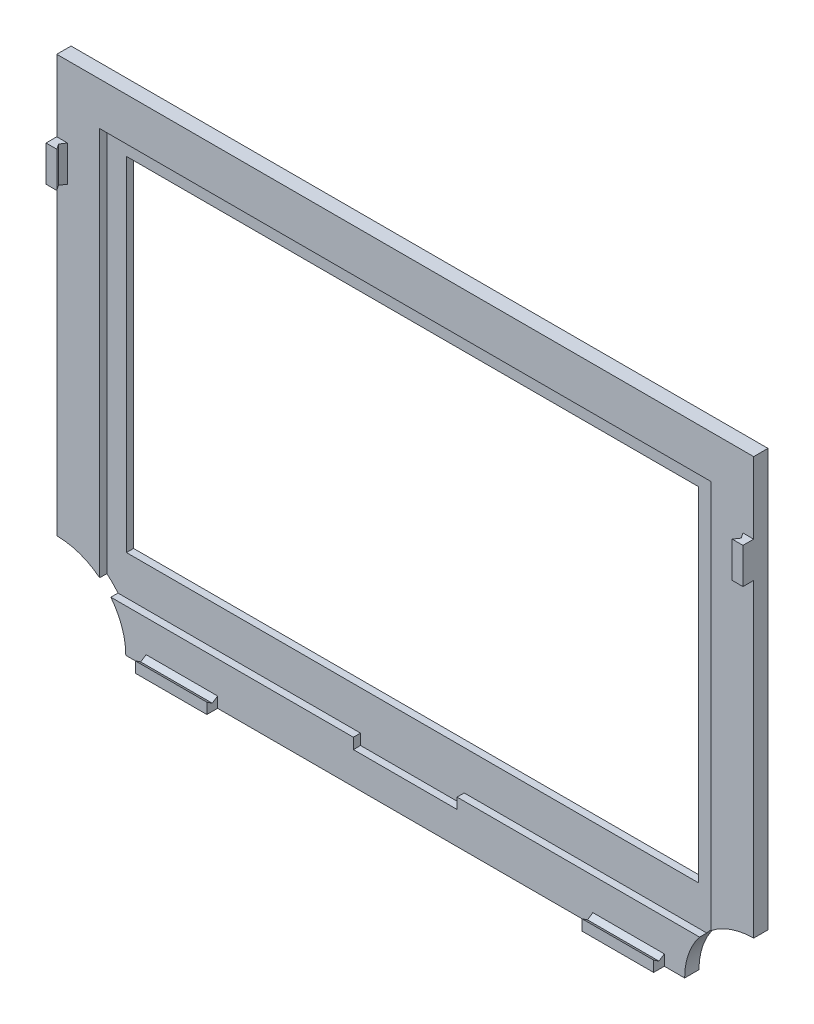
SolidWorks part; units mm, degrees
ref_plane "Front Plane" through (0, 0, 0) normal (0, 0, 1) x (1, 0, 0)
ref_plane "Top Plane" through (0, 0, 0) normal (0, 1, 0) x (1, 0, 0)
ref_plane "Right Plane" through (0, 0, 0) normal (1, 0, 0) x (0, 0, -1)
sketch "Sketch1" plane through (0, 0, 0) normal (0, 0, 1) x (1, 0, 0)
  line L1 (85.5, -56) -> (-85.5, -56)
  line L2 (85.5, -56) -> (85.5, 56)
  line L3 (85.5, 56) -> (-85.5, 56)
  line L4 (-85.5, -56) -> (-85.5, 56)
  line L5 (85.5, -56) -> (-85.5, 56) construction
  line L6 (85.5, 56) -> (-85.5, -56) construction
  line L11 (80, -45) -> (-80, -45)
  line L12 (80, -45) -> (80, 51)
  line L13 (80, 51) -> (-80, 51)
  line L14 (-80, -45) -> (-80, 51)
  line L15 (80, -45) -> (-80, 51) construction
  line L16 (80, 51) -> (-80, -45) construction
  line L17 (-14.5, -56) -> (14.5, -56)
  line L18 (-14.5, -56) -> (-14.5, -59)
  line L19 (-14.5, -59) -> (14.5, -59)
  line L20 (14.5, -56) -> (14.5, -59)
  line L21 (97.5, 68) -> (-97.5, 68)
  line L22 (97.5, 68) -> (97.5, -68)
  line L23 (97.5, -68) -> (-97.5, -68)
  line L24 (-97.5, 68) -> (-97.5, -68)
  line L25 (97.5, 68) -> (-97.5, -68) construction
  line L26 (97.5, -68) -> (-97.5, 68) construction
  point P0 (0, 0)
  point P6 (0, 0)
  point P7 (0, 3)
  point P16 (0, 0)
  dimension "D1" = 171
  dimension "D2" = 112
  dimension "D3" = 96
  dimension "D4" = 160
  dimension "D5" = 5
  dimension "D6" = 71
  dimension "D7" = 29
  dimension "D8" = 3
  dimension "D9" = 12
  dimension "D10" = 17.5
  dimension "D11" = 12
extrude "Boss-Extrude1" add sketch "Sketch1" against normal blind 2 contours L4 L1 L2 L3 L11 L14 L13 L12 | L21 L24 L23 L22 L1 L20 L19 L18 L4 L3 L2 | L20 L1 L18 L19 region at (50, -53.9559, 0) region at (0, -57.5, 0) region at (95.1226, 0, 0)
extrude "Boss-Extrude2" add sketch "Sketch1<3>" along normal blind 2 contours L21 L24 L23 L22 L1 L20 L19 L18 L4 L3 L2 region at (95.1226, 0, 0)
sketch "Sketch1<3>" plane through (0, 0, 0) normal (0, 0, 1) x (1, 0, 0) same geometry as "Sketch1"
ref_plane "Plane1" through (0, 0, 0) normal (0, 0, -1) x (-1, 0, 0)
sketch "Sketch2" plane through (0, 0, 0) normal (0, 0, 1) x (1, 0, 0)
  line L0 (97.5, 68) -> (-97.5, 68) construction
  line L1 (90.5, -61) -> (-90.5, -61) construction
  line L2 (90.5, -61) -> (90.5, 61) construction
  line L3 (90.5, 61) -> (-90.5, 61) construction
  line L4 (-90.5, -61) -> (-90.5, 61) construction
  line L5 (90.5, -61) -> (-90.5, 61) construction
  line L6 (90.5, 61) -> (-90.5, -61) construction
  line L7 (-97.5, 68) -> (-97.5, -68) construction
  line L8 (-90.5, 61) -> (-30.1667, 61) construction
  line L9 (-30.1667, 61) -> (30.1667, 61) construction
  line L10 (30.1667, 61) -> (90.5, 61) construction
  line L11 (-90.5, 61) -> (-30.1667, 61) construction
  line L12 (-30.1667, 61) -> (30.1667, 61) construction
  line L13 (30.1667, 61) -> (90.5, 61) construction
  line L14 (90.5, 61) -> (90.5, 0) construction
  line L15 (90.5, 0) -> (90.5, -61) construction
  circle A0 centre (-90.5, 61) radius 3.25
  circle A2 centre (90.5, 61) radius 3.25
  circle A3 centre (90.5, -61) radius 3.25
  circle A5 centre (-90.5, -61) radius 3.25
  circle A6 centre (-30.1667, -61) radius 3.25
  circle A7 centre (30.1667, -61) radius 3.25
  circle A8 centre (90.5, 0) radius 3.25
  circle A9 centre (-30.1667, 61) radius 3.25
  circle A10 centre (30.1667, 61) radius 3.25
  circle A11 centre (-90.5, 0) radius 3.25
  point P0 (0, 0)
  dimension "D1" = 6.5
  dimension "D2" = 7
  dimension "D3" = 7
extrude "Cut-Extrude1" cut sketch "Sketch2" against normal blind 1.375 and the other way blind 1.375
sketch "Sketch3" plane through (0, 0, -2) normal (0, 0, -1) x (-1, 0, 0)
  circle A0 centre (97.5, -68) radius 19.3143
extrude "Cut-Extrude2" cut sketch "Sketch3" against normal through all
mirror "Mirror1" about plane through (0, 0, 0) normal (1, 0, 0) of "Cut-Extrude2"
sketch "Sketch5" plane through (0, 0, 2) normal (0, 0, 1) x (1, 0, 0)
  line L0 (78.1857, -68) -> (-78.1857, -68) construction
  line L1 (-72.5, -68) -> (-52.5, -68)
  line L2 (-72.5, -68) -> (-72.5, -65)
  line L3 (-72.5, -65) -> (-52.5, -65)
  line L4 (-52.5, -68) -> (-52.5, -65)
  line L5 (-97.5, 68) -> (-97.5, -48.6857) construction
  line L6 (52.5, -68) -> (72.5, -68)
  line L7 (52.5, -68) -> (52.5, -65)
  line L8 (52.5, -65) -> (72.5, -65)
  line L9 (72.5, -68) -> (72.5, -65)
  line L10 (-97.5, 38) -> (-94.5, 38)
  line L11 (-97.5, 38) -> (-97.5, 48)
  line L12 (-97.5, 48) -> (-94.5, 48)
  line L13 (-94.5, 38) -> (-94.5, 48)
  line L14 (97.5, 68) -> (97.5, -48.6857) construction
  line L15 (97.5, 38) -> (94.5, 38)
  line L16 (97.5, 38) -> (97.5, 48)
  line L17 (97.5, 48) -> (94.5, 48)
  line L18 (94.5, 38) -> (94.5, 48)
  line L19 (97.5, 68) -> (-97.5, 68) construction
  dimension "D1" = 3
  dimension "D2" = 10
  dimension "D3" = 20
  dimension "D4" = 25
  dimension "D5" = 25
  dimension "D6" = 20
extrude "Boss-Extrude3" add sketch "Sketch5" along normal blind 3
sketch "Sketch6" plane through (72.5, 0, 0) normal (1, 0, 0) x (0, 0, -1)
  line L0 (-5, -68) -> (-5, -65) construction
  line L1 (-2, -65) -> (-5, -65)
  line L2 (-2, -65) -> (-2, -66)
  line L3 (-2, -66) -> (-5, -66)
  line L4 (-5, -65) -> (-5, -66)
  line L5 (-3.5, -66) -> (-5, -65)
  line L6 (-3.5, -66) -> (-2, -65)
  line M6 (-2, -65) -> (-5, -65)
  dimension "D1" = 1
extrude "Cut-Extrude3" cut sketch "Sketch6" against normal through all contours L5 L6 M6 region at (72.5, -65.3333, 3.5)
sketch "Sketch7" plane through (0, 48, 0) normal (0, 1, 0) x (1, 0, 0)
  line L0 (97.5, -5) -> (94.5, -5) construction
  line L1 (94.5, -2) -> (95.5, -2)
  line L2 (94.5, -2) -> (94.5, -5)
  line L3 (94.5, -5) -> (95.5, -5)
  line L4 (95.5, -2) -> (95.5, -5)
  line L5 (94.5, -5) -> (95.5, -3.5)
  line L6 (94.5, -2) -> (95.5, -3.5)
  line M6 (94.5, -2) -> (94.5, -5)
  dimension "D1" = 1
extrude "Cut-Extrude4" cut sketch "Sketch7" against normal through all contours L6 L5 M6 region at (94.8333, 48, 3.5)
mirror "Mirror2" about plane through (0, 0, 0) normal (1, 0, 0) of "Cut-Extrude4"
